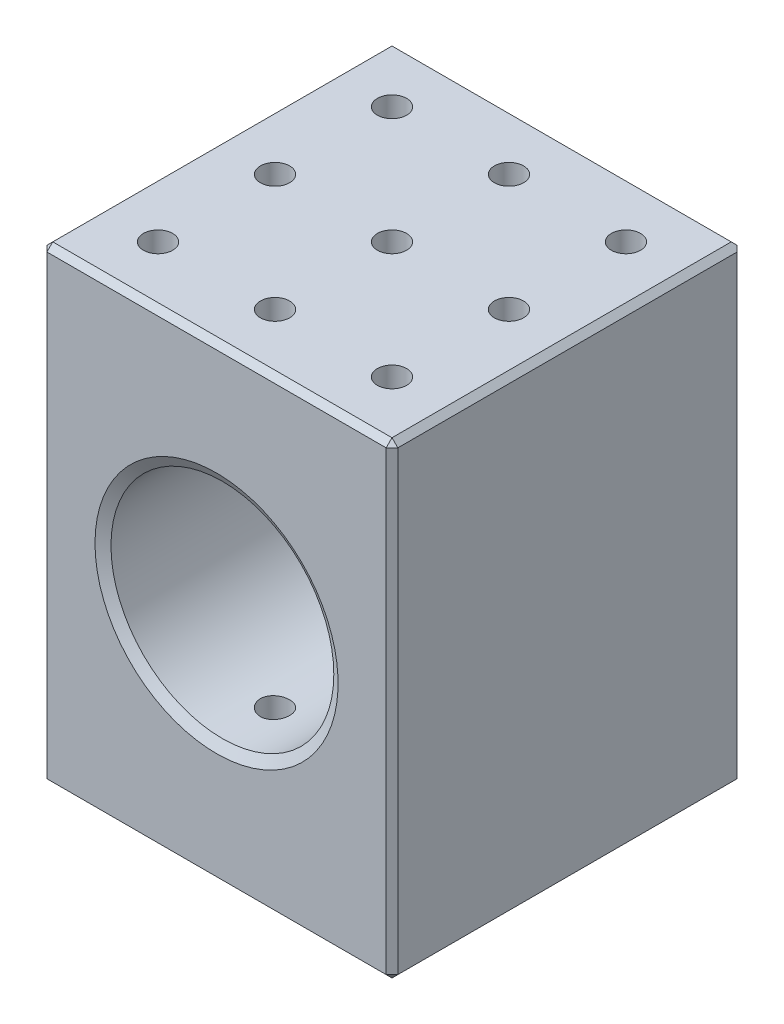
SolidWorks part; units mm, degrees
material "HDPE, Black"
ref_plane "Front Plane" through (0, 0, 0) normal (0, 0, 1) x (1, 0, 0)
ref_plane "Top Plane" through (0, 0, 0) normal (0, 1, 0) x (1, 0, 0)
ref_plane "Right Plane" through (0, 0, 0) normal (1, 0, 0) x (0, 0, -1)
sketch "Sketch1" plane through (0, 0, 0) normal (0, 0, 1) x (1, 0, 0)
  line L3 (-15, -20) -> (15, -20)
  line L4 (-15, -20) -> (-15, 20)
  line L5 (-15, 20) -> (15, 20)
  line L7 (15, 20) -> (15, -20)
  line L8 (0, 20) -> (0, -20) construction
  circle A2 centre (0, 0) radius 9.525
  point P0 (0, 0)
  dimension "D2" = 19.05
  dimension "D3" = 40
  dimension "D1" = 30
extrude "Boss-Extrude1" add sketch "Sketch1" along normal mid plane 30
chamfer "Chamfer2" distance 0.5 angle 60 2 edges at (9.525, 0, -15) (9.525, 0, 15) tangent propagation no first distance on face at (0, 0, -15) first distance on face at (9.525, 0, 15)
chamfer "Chamfer3" distance 0.5 angle 45 2 edges at (0, -20, -15) (0, 20, -15)
mirror "Mirror1" [suppressed]
sketch "Sketch6" plane through (0, 20, 0) normal (0, 1, 0) x (1, 0, 0)
  line L0 (-10, 0) -> (10, 0) construction
  line L2 (-10, -10) -> (10, -10)
  line L3 (-10, -10) -> (-10, 10)
  line L4 (-10, 10) -> (10, 10)
  line L5 (10, -10) -> (10, 10)
  line L6 (-10, -10) -> (10, 10) construction
  line L7 (-10, 10) -> (10, -10) construction
  circle A0 centre (-10, 0) radius 1.9365
  circle A1 centre (10, 0) radius 1.9365
  point P5 (0, 0)
  dimension "D1" = 20
hole_wizard "M3x0.5 Tapped Hole1" positions "Sketch7" profile "Sketch8" tap size "M3x0.5" standard "ANSI Metric"
sketch "Sketch7" plane through (0, 20, 0) normal (0, 1, 0) x (1, 0, 0)
  line L0 (-10, 10) -> (10, 10) construction
  line L1 (-10, -10) -> (10, -10) construction
  point P0 (-10, 0)
  point P3 (10, 0)
  point P6 (0, 0)
  point P9 (-10, 10)
  point P12 (-10, -10)
  point P15 (10, 10)
  point P18 (10, -10)
  point P23 (0, 10)
  point P25 (0, -10)
sketch "Sketch8" plane through (-10, 20, 0) normal (1, 0, 0) x (0, 0, 1)
  line L0 (0, 0) -> (0, 12.7511)
  line L1 (0, 12.7511) -> (1.25, 12)
  line L2 (1.25, 12) -> (1.25, 0)
  line L5 (1.25, 0) -> (0, 0)
  line L10 (0, 12.7511) -> (-1.25, 12) construction
  line L11 (0, -6.35) -> (0, 107.95) construction
  dimension "Tap Drill Dia." = 2.5
  dimension "Tap Drill Depth" = 12
  dimension "Drill Angle" = 118
cosmetic thread "Hole Thread3" parameters "D1"=10, "D2"=3
cosmetic thread "Hole Thread4" parameters "D1"=10, "D2"=3
cosmetic thread "Hole Thread9" parameters "D1"=10, "D2"=3
cosmetic thread "Hole Thread10" parameters "D1"=10, "D2"=3
cosmetic thread "Hole Thread11" parameters "D1"=10, "D2"=3
cosmetic thread "Hole Thread12" parameters "D1"=10, "D2"=3
cosmetic thread "Hole Thread13" parameters "D1"=10, "D2"=3
cosmetic thread "Hole Thread14" parameters "D1"=10, "D2"=3
cosmetic thread "Hole Thread15" parameters "D1"=10, "D2"=3
sketch "Sketch9" [suppressed] plane through (0, 0, -14.25) normal (0, 0, -1) x (-1, 0, 0)
  line L1 (0, -12) -> (-25, -12)
  line L4 (0, 0) -> (0, -12) construction
  line L5 (88, -14) -> (-88, -14) construction
  line L6 (0, -12) -> (0, -15)
  line L7 (0, -15) -> (-80, -15)
  line L8 (-80, -15) -> (-80, -14)
  arc A2 (-80, -14) -> (-78.9832, -13.963) centre (-80, 0) ccw
  arc A3 (-25, -12) -> (-78.9832, -13.963) centre (-25, -755.25) ccw
  line M13 (-88, -13.5) -> (88, -13.5)
  dimension "D1" = 50
  dimension "D3" = 12
extrude "Cut-Extrude1" [suppressed] cut sketch "Sketch9" against normal through all contours L1 A3 A2 L6 M13 | A2 L8 L7 L6 M13
mirror "Mirror2" [suppressed]
chamfer "Chamfer4" [suppressed] distance 0.5 angle 45
sketch "Sketch10" plane through (0, 0, -15) normal (0, 0, -1) x (-1, 0, 0)
  circle A0 centre (0, 0) radius 11
  dimension "D1" = 22
extrude "Cut-Extrude2" [suppressed] cut sketch "Sketch10" against normal through all
chamfer "Chamfer5" [suppressed] distance 0.254 angle 45
sketch "Sketch11" [suppressed] plane through (0, -12, 0) normal (0, -1, 0) x (1, 0, 0)
  line L0 (12.7, 0) -> (-12.7, 0) construction
  dimension "D1" = 25.4
hole_wizard "M4x0.7 Tapped Hole1" [suppressed] positions "Sketch12" profile "Sketch14" tap size "M4x0.7" standard "ANSI Metric"
sketch "Sketch12" [suppressed] plane through (0, -14, 0) normal (0, -1, 0) x (-1, 0, 0)
  point P0 (-12.7, 0)
  point P3 (12.7, 0)
sketch "Sketch14" plane through (12.7, -14, 0) normal (1, 0, 0) x (0, 0, -1)
  line L0 (0, 0) -> (0, 11.0914)
  line L1 (0, 11.0914) -> (1.65, 10.1)
  line L2 (1.65, 10.1) -> (1.65, 0)
  line L5 (1.65, 0) -> (0, 0)
  line L10 (0, 11.0914) -> (-1.65, 10.1) construction
  line L11 (0, -6.35) -> (0, 107.95) construction
  dimension "Tap Drill Dia." = 3.3
  dimension "Tap Drill Depth" = 10.1
  dimension "Drill Angle" = 118
cosmetic thread "Hole Thread5" parameters "D1"=8, "D2"=4
cosmetic thread "Hole Thread6" parameters "D1"=8, "D2"=4
sketch "Sketch15" plane through (0, -20, 0) normal (0, -1, 0) x (1, 0, 0)
  circle A0 centre (0, 0) radius 12.7 construction
  dimension "D1" = 25.4
pattern_circular "CirPattern1" count 2 over 360 about axis through (0, 0, 15) along (0, 0, -1) of "M3x0.5 Tapped Hole1"
chamfer "Chamfer6" distance 0.5 angle 45 10 edges at (15, 0, -15) (-15, 0, -15) (15, 0, 15) (15, 20, 0.25) (0, 20, 15) (-15, 20, 0.25) (-15, -20, 0.25) (15, -20, 0.25) (0, -20, 15) (-15, 0, 15)
